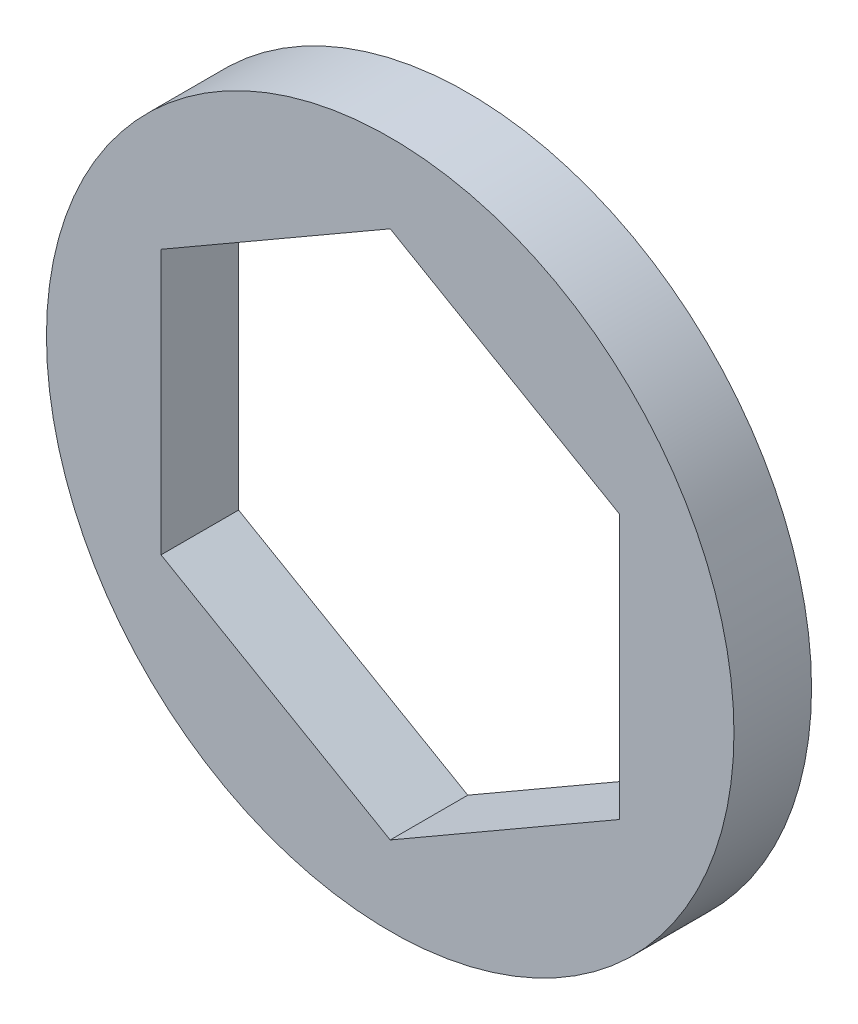
SolidWorks part; units mm, degrees
material "Nylon 101"
ref_plane "Front Plane" through (0, 0, 0) normal (0, 0, 1) x (1, 0, 0)
ref_plane "Top Plane" through (0, 0, 0) normal (0, 1, 0) x (1, 0, 0)
ref_plane "Right Plane" through (0, 0, 0) normal (1, 0, 0) x (0, 0, -1)
sketch "Sketch1" plane through (0, 0, 0) normal (0, 0, 1) x (1, 0, 0)
  line L1 (0, 7.3323) -> (-6.35, 3.6662)
  line L2 (-6.35, 3.6662) -> (-6.35, -3.6662)
  line L3 (-6.35, -3.6662) -> (0, -7.3323)
  line L4 (0, -7.3323) -> (6.35, -3.6662)
  line L5 (6.35, -3.6662) -> (6.35, 3.6662)
  line L6 (6.35, 3.6662) -> (0, 7.3323)
  circle A0 centre (0, 0) radius 9.525
  circle A1 centre (0, 0) radius 6.35 construction
  point P3 (0, 0)
  dimension "D1" = 12.7
  dimension "D2" = 19.05
extrude "Boss-Extrude1" add sketch "Sketch1" along normal mid plane 2.1496
